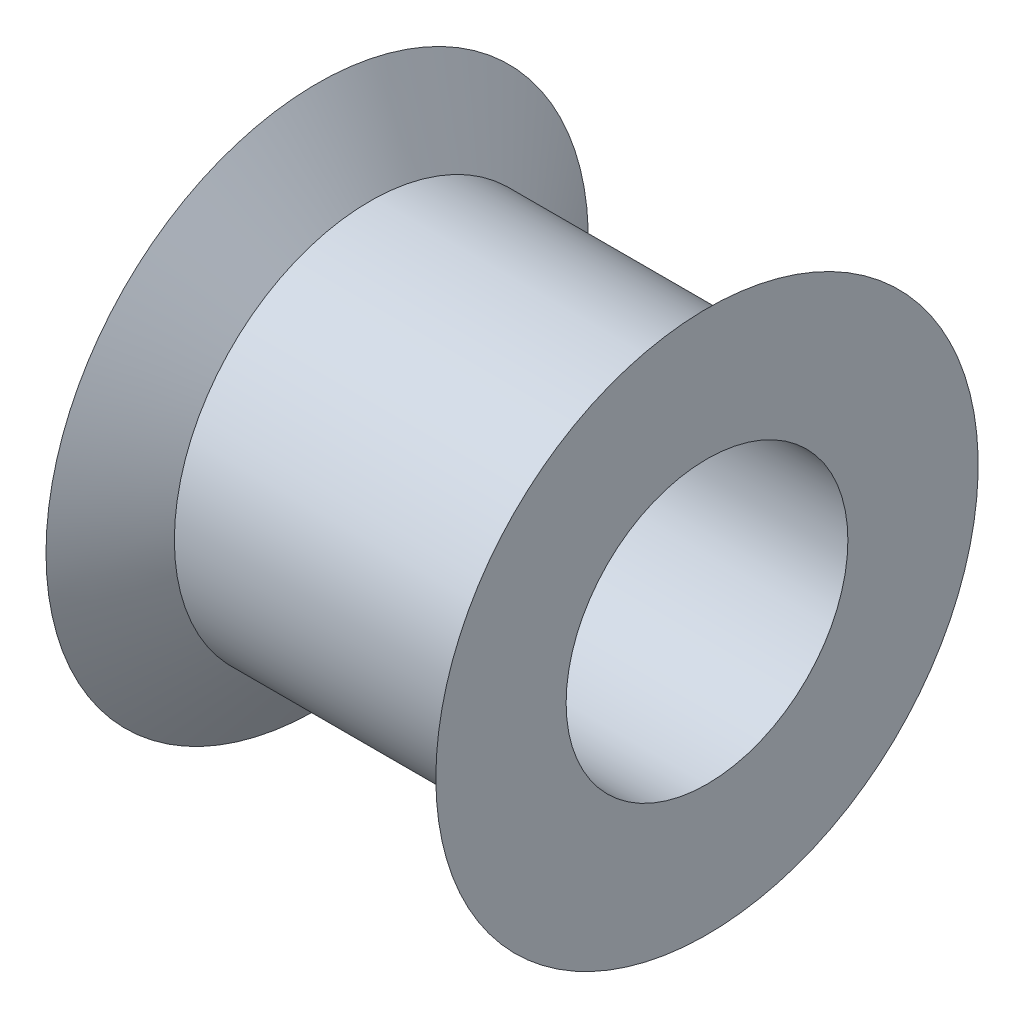
SolidWorks part; units mm, degrees
ref_plane "Front Plane" through (0, 0, 0) normal (0, 0, 1) x (1, 0, 0)
ref_plane "Top Plane" through (0, 0, 0) normal (0, 1, 0) x (1, 0, 0)
ref_plane "Right Plane" through (0, 0, 0) normal (1, 0, 0) x (0, 0, -1)
sketch "Sketch2" plane through (0, 0, 0) normal (0, 0, 1) x (1, 0, 0)
  line L0 (0, 2.286) -> (6.3256, 2.286)
  line L1 (6.3256, 2.286) -> (6.3256, 4.4)
  line L2 (0, 0) -> (14.6931, 0) construction
  line L3 (0, 2.286) -> (0, 4.4)
  line L4 (0.8578, 3.175) -> (5.4678, 3.175)
  line L5 (0, 4.4) -> (0.8578, 3.175)
  line L6 (5.4678, 3.175) -> (6.3256, 4.4)
  line L8 (6.3256, 6.3086) -> (6.3256, -1.2716) construction
  point P9 (3.1628, 3.175)
  point P10 (3.1628, 2.286)
  point P11 (0, 0)
  point P12 (0, 0)
  point P13 (-0.0244, 4.6253)
  point P14 (0, 4.4)
  point P17 (0.8623, 3.41)
  dimension "D1" = 4.572
  dimension "D2" = 6.35
  dimension "D3" = 35
revolve "Revolve1" add sketch "Sketch2" angle 360 about L2
